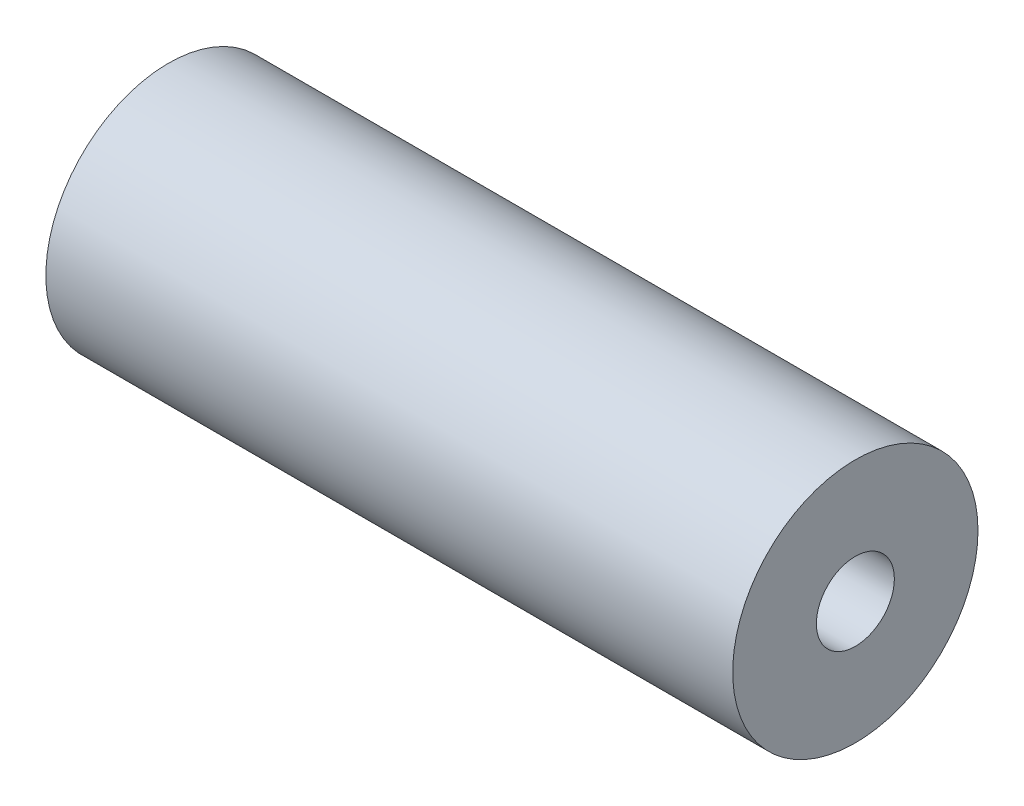
SolidWorks part; units mm, degrees
material "6061-T6 (SS)"
ref_plane "Front Plane" through (0, 0, 0) normal (0, 0, 1) x (1, 0, 0)
ref_plane "Top Plane" through (0, 0, 0) normal (0, 1, 0) x (1, 0, 0)
ref_plane "Right Plane" through (0, 0, 0) normal (1, 0, 0) x (0, 0, -1)
sketch "Sketch1" plane through (0, 0, 0) normal (1, 0, 0) x (0, 0, -1)
  circle A0 centre (0, 0) radius 6.35
  dimension "D1" = 12.7
extrude "Boss-Extrude1" add sketch "Sketch1" along normal mid plane 35.56
hole_wizard "Tap Drill for #10-32 Tap1" positions "Sketch2" profile "Sketch4" hole size "#10-32" standard "ANSI Inch"
sketch "Sketch2" plane through (17.78, 0, 0) normal (1, 0, 0) x (0, 0, -1)
  point P0 (0, 0)
sketch "Sketch4" plane through (17.78, 0, 0) normal (0, 1, 0) x (0, 0, -1)
  line L0 (0, 0) -> (0, 12.1353)
  line L1 (0, 12.1353) -> (2.0193, 10.922)
  line L2 (2.0193, 10.922) -> (2.0193, 0)
  line L5 (2.0193, 0) -> (0, 0)
  line L10 (0, 12.1353) -> (-2.0193, 10.922) construction
  line L11 (0, -6.35) -> (0, 107.95) construction
  dimension "Hole Dia." = 4.0386
  dimension "Hole Depth" = 10.922
  dimension "Drill Angle" = 118
mirror "Mirror1" about plane through (0, 0, 0) normal (1, 0, 0) of "Tap Drill for #10-32 Tap1"
